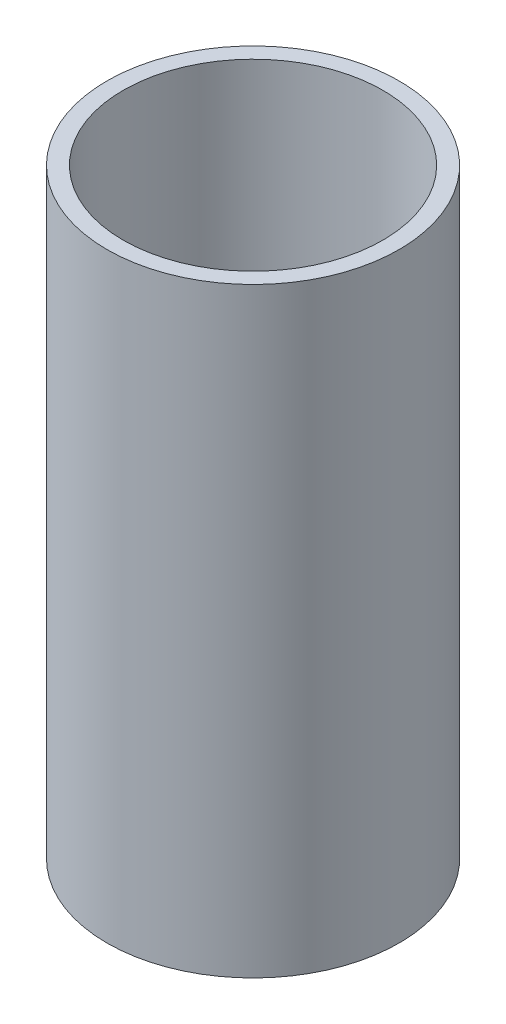
SolidWorks part; units mm, degrees
ref_plane "Front Plane" through (0, 0, 0) normal (0, 0, 1) x (1, 0, 0)
ref_plane "Top Plane" through (0, 0, 0) normal (0, 1, 0) x (1, 0, 0)
ref_plane "Right Plane" through (0, 0, 0) normal (1, 0, 0) x (0, 0, -1)
sketch "Sketch1" plane through (0, 0, 0) normal (0, 1, 0) x (1, 0, 0)
  circle A0 centre (0, 0) radius 11.43
  circle A1 centre (0, 0) radius 10.16
  dimension "D1" = 1.27
extrude "Boss-Extrude1" add sketch "Sketch1" along normal blind 46.99
